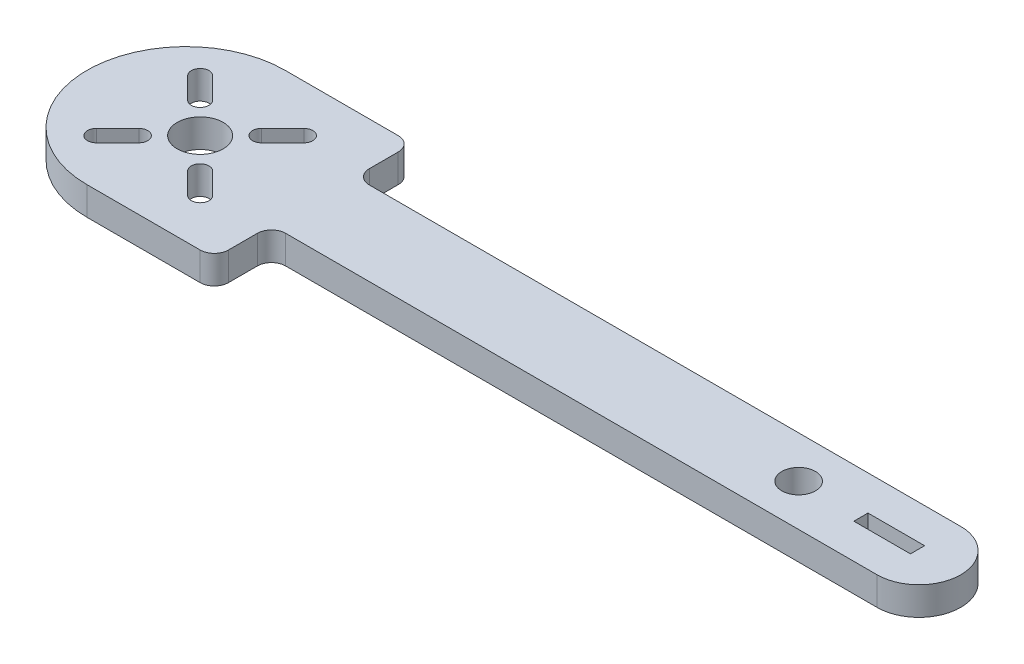
SolidWorks part; units mm, degrees
material "Thornel VCB-20 Carbon Cloth"
ref_plane "Front Plane" through (0, 0, 0) normal (0, 0, 1) x (1, 0, 0)
ref_plane "Top Plane" through (0, 0, 0) normal (0, 1, 0) x (1, 0, 0)
ref_plane "Right Plane" through (0, 0, 0) normal (1, 0, 0) x (0, 0, -1)
sketch "Sketch1" plane through (0, 0, 0) normal (0, 1, 0) x (1, 0, 0)
  line L0 (-58.0134, 7.2134) -> (-43.5866, -7.2134) construction
  line L1 (-50.8, 14) -> (-36.8, 14)
  line L2 (-50.8, 14) -> (-50.8, -14) construction
  line L3 (-50.8, -14) -> (-36.8, -14)
  line L7 (-58.4887, -7.6887) -> (-43.1113, 7.6887) construction
  line L8 (-58.1362, 7.3362) -> (-55.131, 4.331) construction
  line L9 (-57.2523, 8.2201) -> (-54.2471, 5.2149)
  line L10 (-59.0201, 6.4523) -> (-56.0149, 3.4471)
  line L11 (-43.4638, 7.3362) -> (-46.469, 4.331) construction
  line L12 (-42.5799, 6.4523) -> (-45.5851, 3.4471)
  line L13 (-44.3477, 8.2201) -> (-47.3529, 5.2149)
  line L14 (-43.4638, -7.3362) -> (-46.469, -4.331) construction
  line L15 (-44.3477, -8.2201) -> (-47.3529, -5.2149)
  line L16 (-42.5799, -6.4523) -> (-45.5851, -3.4471)
  line L17 (-58.1362, -7.3362) -> (-55.131, -4.331) construction
  line L18 (-59.0201, -6.4523) -> (-56.0149, -3.4471)
  line L19 (-57.2523, -8.2201) -> (-54.2471, -5.2149)
  line L21 (-34.8, 7.9146) -> (-34.8, 12)
  line L24 (-34.8, -12) -> (-34.8, -7.9146)
  line L32 (-32.8, 5.9146) -> (50.8, 5.9146)
  line L33 (-32.8, -5.9146) -> (50.8, -5.9146)
  line L34 (-50.8, 0) -> (50.8, 0) construction
  line L35 (-50.8, 14) -> (-52.8, 14)
  line L36 (-50.8, -14) -> (-52.8, -14)
  line L38 (42.6, -1) -> (50.6, -1)
  line L39 (42.6, -1) -> (42.6, 1)
  line L40 (42.6, 1) -> (50.6, 1)
  line L41 (50.6, -1) -> (50.6, 1)
  line L42 (42.6, -1) -> (50.6, 1) construction
  line L43 (42.6, 1) -> (50.6, -1) construction
  circle A2 centre (-50.8, 0) radius 3.25
  arc A3 (-57.2523, 8.2201) -> (-59.0201, 6.4523) centre (-58.1362, 7.3362) ccw
  arc A4 (-56.0149, 3.4471) -> (-54.2471, 5.2149) centre (-55.131, 4.331) ccw
  arc A5 (-42.5799, 6.4523) -> (-44.3477, 8.2201) centre (-43.4638, 7.3362) ccw
  arc A6 (-47.3529, 5.2149) -> (-45.5851, 3.4471) centre (-46.469, 4.331) ccw
  arc A7 (-44.3477, -8.2201) -> (-42.5799, -6.4523) centre (-43.4638, -7.3362) ccw
  arc A8 (-45.5851, -3.4471) -> (-47.3529, -5.2149) centre (-46.469, -4.331) ccw
  arc A9 (-59.0201, -6.4523) -> (-57.2523, -8.2201) centre (-58.1362, -7.3362) ccw
  arc A10 (-54.2471, -5.2149) -> (-56.0149, -3.4471) centre (-55.131, -4.331) ccw
  arc A12 (-34.8, -7.9146) -> (-32.8, -5.9146) centre (-32.8, -7.9146) cw
  arc A13 (-32.8, 5.9146) -> (-34.8, 7.9146) centre (-32.8, 7.9146) cw
  arc A14 (-36.8, -14) -> (-34.8, -12) centre (-36.8, -12) ccw
  arc A15 (-34.8, 12) -> (-36.8, 14) centre (-36.8, 12) ccw
  arc A16 (50.8, 5.9146) -> (50.8, -5.9146) centre (50.8, 0) cw
  arc A17 (-52.8, -14) -> (-52.8, 14) centre (-52.8, 0) cw
  circle A18 centre (33.8, 0) radius 2.3812
  point P0 (0, 0)
  point P12 (-50.8, 0)
  point P14 (-50.8, 0)
  point P17 (-56.6336, 5.8336)
  point P27 (-44.9664, 5.8336)
  point P34 (-44.9664, -5.8336)
  point P41 (-56.6336, -5.8336)
  point P46 (-50.8, 0)
  point P53 (-34.8, -7)
  point P56 (-34.8, 7)
  point P59 (-34.8, -14)
  point P62 (-34.8, 14)
  point P64 (46.6, 0)
  dimension "D3" = 6.5
  dimension "D6" = 8.25
  dimension "D10" = 4.7625
  dimension "D17" = 2
  dimension "D18" = 2
  dimension "D16" = 5.9146
  dimension "D2" = 14
  dimension "D21" = 2
  dimension "D22" = 8
  dimension "D4" = 45
  dimension "D5" = 45
  dimension "D7" = 4.25
  dimension "D8" = 2.5
  dimension "D11" = 16
  dimension "D12" = 16
  dimension "D13" = 7
  dimension "D14" = 7
  dimension "D15" = 101.6
  dimension "D19" = 50.8
  dimension "D20" = 2
  dimension "D23" = 4.2
  dimension "D24" = 17
  dimension "D9" = 4
extrude "Boss-Extrude1" add sketch "Sketch1" along normal blind 4
